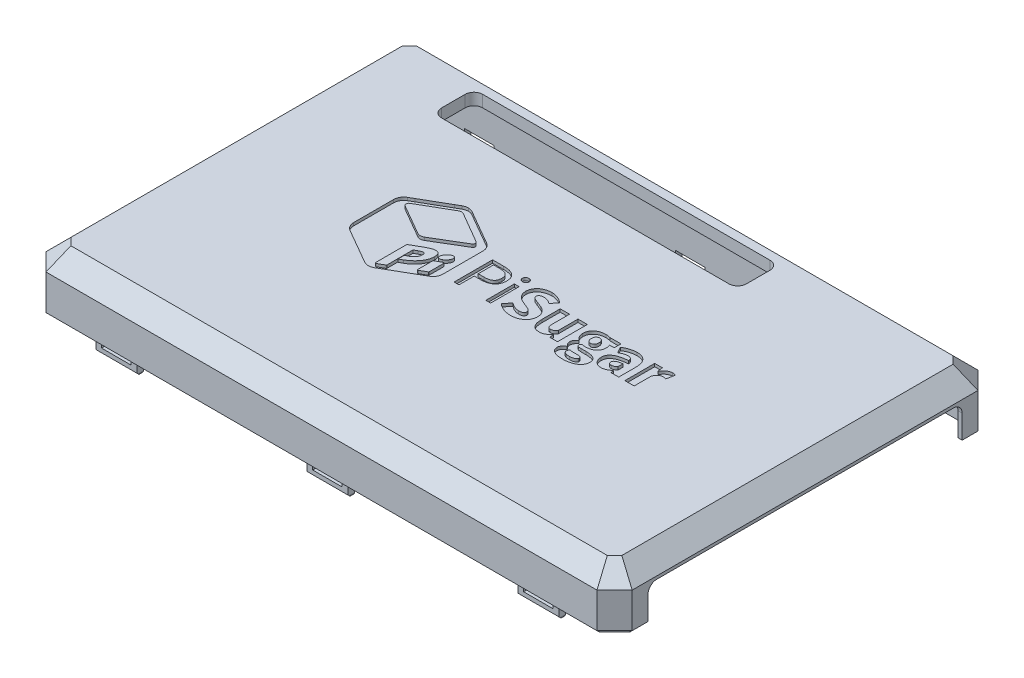
SolidWorks part; units mm, degrees
ref_plane "前视基准面" through (0, 0, 0) normal (0, 0, 1) x (1, 0, 0)
ref_plane "上视基准面" through (0, 0, 0) normal (0, 1, 0) x (1, 0, 0)
ref_plane "右视基准面" through (0, 0, 0) normal (1, 0, 0) x (0, 0, -1)
sketch "草图1" plane through (0, 0, 0) normal (0, 1, 0) x (1, 0, 0)
  line L1 (-50, 32.5) -> (50, 32.5)
  line L2 (-50, 32.5) -> (-50, -32.5)
  line L3 (-50, -32.5) -> (50, -32.5)
  line L4 (50, 32.5) -> (50, -32.5)
  line L5 (-50, 32.5) -> (50, -32.5) construction
  line L6 (-50, -32.5) -> (50, 32.5) construction
  point P0 (0, 0)
  dimension "D1" = 100
  dimension "D2" = 65
extrude "凸台-拉伸1" add sketch "草图1" along normal blind 2
sketch "草图4" plane through (0, 0, 0) normal (0, -1, 0) x (1, 0, 0)
  line L4 (-50, -32.5) -> (50, -32.5)
  line L5 (50, -32.5) -> (50, 32.5)
  line L6 (50, 32.5) -> (-50, 32.5)
  line L7 (-50, 32.5) -> (-50, -32.5)
  line L8 (-47.9, -30.4) -> (47.9, -30.4)
  line L9 (47.9, -30.4) -> (47.9, 30.4)
  line L10 (47.9, 30.4) -> (-47.9, 30.4)
  line L11 (-47.9, 30.4) -> (-47.9, -30.4)
  line L12 (-47.9, -30.4) -> (47.9, -30.4)
  line L13 (47.9, -30.4) -> (47.9, 30.4)
  line L14 (47.9, 30.4) -> (-47.9, 30.4)
  line L15 (-47.9, 30.4) -> (-47.9, -30.4)
  line L16 (-50, -32.5) -> (50, -32.5)
  line L17 (50, -32.5) -> (50, 32.5)
  line L18 (50, 32.5) -> (-50, 32.5)
  line L19 (-50, 32.5) -> (-50, -32.5)
  dimension "D1" = 2.1
  dimension "D2" = 0
extrude "凸台-拉伸2" add sketch "草图4" along normal blind 7
sketch "草图21" plane through (-50, 0, 0) normal (-1, 0, 0) x (0, 0, 1)
  line L0 (-32.5, 2) -> (32.5, 2) construction
  line L1 (-10, -2) -> (10, -2)
  line L2 (-10, -2) -> (-10, -4)
  line L3 (-10, -4) -> (10, -4)
  line L4 (10, -2) -> (10, -4)
  line L5 (-10, -2) -> (10, -4) construction
  line L6 (-10, -4) -> (10, -2) construction
  point P0 (0, -3)
  point P8 (0, 2)
  dimension "D1" = 4
  dimension "D2" = 2
  dimension "D3" = 20
chamfer "倒角4" distance 2 angle 45 4 edges at (47.9, -3.5, -30.4) (-47.9, -3.5, -30.4) (-47.9, -3.5, 30.4) (47.9, -3.5, 30.4)
chamfer "倒角5" distance 3 angle 45 4 edges at (-50, -2.5, -32.5) (-50, -2.5, 32.5) (50, -2.5, -32.5) (50, -2.5, 32.5)
chamfer "倒角7" distance 3 angle 45 8 edges at (48.5, 2, -31) (50, 2, 0) (48.5, 2, 31) (0, 2, 32.5) (-48.5, 2, 31) (-50, 2, 0) (0, 2, -32.5) (-48.5, 2, -31)
sketch "草图24" plane through (47.9, 0, 0) normal (-1, 0, 0) x (0, 0, 1)
  line L0 (-28.4, -7) -> (28.4, -7) construction
  line L1 (-28.3, -7) -> (28.3, -7)
  line L2 (-28.3, -7) -> (-28.3, -1)
  line L3 (-28.3, -1) -> (28.3, -1)
  line L4 (28.3, -7) -> (28.3, -1)
  line L6 (-32.5, -1) -> (-32.5, -7) construction
  line L7 (32.5, -7) -> (32.5, -1) construction
  line L8 (28.2574, 2) -> (-28.2574, 2) construction
  dimension "D1" = 4.2
  dimension "D2" = 4.2
  dimension "D3" = 3
extrude "切除-拉伸8" cut sketch "草图24" against normal blind 1.4
fillet "圆角9" radius 2 2 edges at (48.6, -1, 28.3) (48.6, -1, -28.3)
sketch "草图25" plane through (49.3, 0, 0) normal (-1, 0, 0) x (0, 0, 1)
  line L0 (-32.5, -1) -> (-32.5, -7) construction
  line L1 (32.5, -7) -> (32.5, -1) construction
  line L4 (-28.3, -7) -> (28.3, -7) construction
  line L12 (26.8, -7) -> (26.8, -3)
  line L13 (25.3, -1.5) -> (-25.3, -1.5)
  line L14 (-26.8, -3) -> (-26.8, -7)
  line L15 (-26.8, -7) -> (26.8, -7)
  arc A6 (26.8, -3) -> (25.3, -1.5) centre (25.3, -3) ccw
  arc A7 (-25.3, -1.5) -> (-26.8, -3) centre (-25.3, -3) ccw
  dimension "D1" = 7.2
  dimension "D2" = 7.2
extrude "切除-拉伸9" cut sketch "草图25" against normal blind 11.4
sketch "草图26" plane through (0, -7, 0) normal (0, -1, 0) x (1, 0, 0)
  line L0 (45.9, 30.4) -> (47.9, 28.4)
  line L1 (-45.9, -30.4) -> (45.9, -30.4)
  line L2 (-47.9, -28.4) -> (-47.9, 28.4)
  line L3 (-45.9, 30.4) -> (45.9, 30.4)
  line L5 (-47.9, 28.4) -> (-45.9, 30.4)
  line L6 (-47.9, -28.4) -> (-45.9, -30.4)
  line L7 (45.9, -30.4) -> (47.9, -28.4)
  line L8 (-49, -28.8556) -> (-49, 28.8556)
  line L9 (-49, 28.8556) -> (-46.3556, 31.5)
  line L10 (-46.3556, 31.5) -> (46.3556, 31.5)
  line L11 (46.3556, 31.5) -> (49, 28.8556)
  line L13 (46.3556, -31.5) -> (49, -28.8556)
  line L14 (-46.3556, -31.5) -> (46.3556, -31.5)
  line L15 (-49, -28.8556) -> (-46.3556, -31.5)
  line L16 (45.9, 30.4) -> (-45.9, 30.4) construction
  line L17 (49, -28.8556) -> (49, 28.8556) construction
  line L18 (47.9, -28.4) -> (47.9, 28.4) construction
  line L19 (49, 28.8556) -> (49, 28.3)
  line L21 (49, 28.3) -> (47.9, 28.3)
  line L23 (47.9, 28.3) -> (47.9, 28.4)
  line L24 (49, -28.8556) -> (49, -28.3)
  line L26 (49, -28.3) -> (47.9, -28.3)
  line L28 (47.9, -28.3) -> (47.9, -28.4)
  line L29 (49.3, -28.3) -> (47.9, -28.3) construction
  line L30 (49.3, 28.3) -> (47.9, 28.3) construction
  point P0 (-47.9, -30.4)
  point P1 (47.9, 30.4)
  point P2 (-47.9, 30.4)
  point P3 (47.9, -30.4)
  dimension "D2" = 56.8
  dimension "D7" = 91.8
  dimension "D1" = 1.1
extrude "凸台-拉伸9" add sketch "草图26" along normal blind 1
sketch "草图29" plane through (0, 2, 0) normal (0, 1, 0) x (1, 0, 0)
  line B0 (-10.6869, 6.36) -> (-11.5075, 6.833)
  line B1 (-11.5075, 6.833) -> (-15.7643, 9.2891)
  line B2 (-15.7643, 9.2891) -> (-16.5849, 9.7678)
  line B3 (-18.3059, 9.7678) -> (-19.1266, 9.2891)
  line B4 (-19.1266, 9.2891) -> (-23.3834, 6.833)
  line B5 (-23.3834, 6.833) -> (-24.2041, 6.36)
  line B6 (-25.0646, 4.8726) -> (-25.0646, -1.943)
  line B7 (-24.2041, -3.4303) -> (-23.3834, -3.9033)
  line B8 (-23.3834, -3.9033) -> (-19.1266, -6.3594)
  line B9 (-19.1266, -6.3594) -> (-18.3059, -6.8381)
  line B10 (-16.5849, -6.8381) -> (-15.7643, -6.3594)
  line B11 (-15.7643, -6.3594) -> (-11.5075, -3.9033)
  line B12 (-11.5075, -3.9033) -> (-10.6869, -3.4303)
  line B13 (-9.8264, -1.943) -> (-9.8264, 4.8726)
  line B14 (-23.1099, 5.6818) -> (-17.8444, 8.7249)
  line B15 (-17.0408, 8.7249) -> (-11.8038, 5.6761)
  line B16 (-11.7981, 4.9752) -> (-16.887, 1.9321)
  line B17 (-15.3084, -3.2252) -> (-15.9011, -3.5557)
  line B18 (-15.9582, -3.6526) -> (-15.9582, -5.3622)
  line B19 (-16.0151, -5.459) -> (-17.1206, -6.0859)
  line B20 (-17.2859, -5.989) -> (-17.2859, -0.712)
  line B21 (-17.2289, -0.6152) -> (-15.3484, 0.4505)
  line B22 (-11.4049, -2.8719) -> (-12.499, -3.493)
  line B23 (-12.6643, -3.3961) -> (-12.6643, -0.883)
  line B24 (-12.6073, -0.7861) -> (-11.5132, -0.1707)
  line B25 (-11.3479, -0.2676) -> (-11.3479, -2.775)
  line B26 (-15.3769, -2.2108) -> (-15.9011, -2.4729)
  line B27 (-15.9582, -2.3533) -> (-15.9582, -1.0084)
  line B28 (-15.9011, -0.9115) -> (-15.411, -0.638)
  line B29 (-5.8316, 4.3939) -> (-7.7065, 4.3939)
  line B30 (-7.7065, 4.3939) -> (-7.7065, -2.1709)
  line B31 (-7.7065, -2.1709) -> (-6.8745, -2.1709)
  line B32 (-6.8745, -2.1709) -> (-6.8745, 0.4334)
  line B33 (-6.8745, 0.4334) -> (-5.786, 0.4334)
  line B34 (-5.8942, 1.1058) -> (-6.8745, 1.1058)
  line B35 (-6.8745, 1.1058) -> (-6.8745, 3.7215)
  line B36 (-6.8745, 3.7215) -> (-5.9285, 3.7215)
  line B37 (-2.2928, 2.6957) -> (-2.2928, -2.1709)
  line B38 (-2.2928, -2.1709) -> (-1.4778, -2.1709)
  line B39 (-1.4778, -2.1709) -> (-1.4778, 2.6957)
  line B40 (-1.4778, 2.6957) -> (-2.2928, 2.6957)
  line B41 (3.2292, 1.6187) -> (2.3973, 1.9492)
  line B42 (3.554, 2.7356) -> (4.3519, 3.7386)
  line B43 (1.1208, 0.7753) -> (1.9699, 0.4163)
  line B44 (0.4198, -0.2334) -> (-0.4862, -1.3389)
  line B45 (8.3353, 2.9237) -> (8.3353, -0.4157)
  line B46 (6.8935, -0.0282) -> (6.8935, 2.9237)
  line B47 (6.8935, 2.9237) -> (5.3036, 2.9237)
  line B48 (5.3036, 2.9237) -> (5.3036, -0.2277)
  line B49 (8.4835, -1.47) -> (8.5176, -1.47)
  line B50 (8.5176, -1.47) -> (8.6316, -2.1709)
  line B51 (8.6316, -2.1709) -> (9.9309, -2.1709)
  line B52 (9.9309, -2.1709) -> (9.9309, 2.9237)
  line B53 (9.9309, 2.9237) -> (8.3353, 2.9237)
  line B54 (13.7832, -1.1679) -> (12.9796, -1.1679)
  line B55 (14.8773, 1.7726) -> (15.6637, 1.7726)
  line B56 (15.6637, 1.7726) -> (15.6637, 2.9237)
  line B57 (15.6637, 2.9237) -> (13.7946, 2.9237)
  line B58 (11.5436, -0.1194) -> (11.5436, -0.1536)
  line B59 (11.4467, -1.9829) -> (11.4467, -2.0284)
  line B60 (12.9967, -2.3875) -> (13.4812, -2.3875)
  line B61 (16.1196, 2.3823) -> (16.6781, 1.3338)
  line B62 (18.9234, -1.658) -> (18.9632, -1.658)
  line B63 (18.9632, -1.658) -> (19.0772, -2.1709)
  line B64 (19.0772, -2.1709) -> (20.3765, -2.1709)
  line B65 (20.3765, -2.1709) -> (20.3765, 0.724)
  line B66 (18.7809, 0.1598) -> (18.7809, -0.6551)
  line B67 (22.8669, 2.0404) -> (22.8326, 2.0404)
  line B68 (22.8326, 2.0404) -> (22.7244, 2.9237)
  line B69 (22.7244, 2.9237) -> (21.4251, 2.9237)
  line B70 (21.4251, 2.9237) -> (21.4251, -2.1709)
  line B71 (21.4251, -2.1709) -> (23.0093, -2.1709)
  line B72 (23.0093, -2.1709) -> (23.0093, 0.7411)
  line B73 (24.6676, 1.5731) -> (24.9354, 2.9465)
  line B74 (-15.9011, -2.4729) -> (-15.9011, -3.5557)
  line B75 (-15.9582, -2.3533) -> (-15.9582, -3.6526)
  spline B76 degree 3 poles (-16.5849, 9.7678) (-16.8528, 9.9159) (-17.1491, 9.9957) (-17.4454, 9.9957) knots 3 3 3 3 4 4 4 4
  spline B77 degree 3 poles (-17.4454, 9.9957) (-17.7418, 9.9957) (-18.0381, 9.9159) (-18.3059, 9.7678) knots 4 4 4 4 5 5 5 5
  spline B78 degree 3 poles (-24.2041, 6.36) (-24.734, 6.0523) (-25.0646, 5.4824) (-25.0646, 4.8726) knots 8 8 8 8 9 9 9 9
  spline B79 degree 3 poles (-25.0646, -1.943) (-25.0646, -2.5584) (-24.734, -3.1226) (-24.2041, -3.4303) knots 10 10 10 10 11 11 11 11
  spline B80 degree 3 poles (-18.3059, -6.8381) (-18.0381, -6.992) (-17.7418, -7.0661) (-17.4454, -7.0661) knots 14 14 14 14 15 15 15 15
  spline B81 degree 3 poles (-17.4454, -7.0661) (-17.1491, -7.0661) (-16.8528, -6.992) (-16.5849, -6.8381) knots 15 15 15 15 16 16 16 16
  spline B82 degree 3 poles (-10.6869, -3.4303) (-10.1512, -3.1226) (-9.8264, -2.5584) (-9.8264, -1.943) knots 19 19 19 19 20 20 20 20
  spline B83 degree 3 poles (-9.8264, 4.8726) (-9.8264, 5.4824) (-10.1512, 6.0523) (-10.6869, 6.36) knots 21 21 21 21 22 22 22 22
  spline B84 degree 2 poles (-17.9982, 1.9321) (-23.1498, 4.9068) (-23.1612, 4.9125) knots 0 0 0 1 1 1
  spline B85 degree 3 poles (-23.1612, 4.9125) (-23.429, 5.1063) (-23.4006, 5.5166) (-23.1099, 5.6818) knots 1 1 1 1 2 2 2 2
  spline B86 degree 3 poles (-17.8444, 8.7249) (-17.5993, 8.8674) (-17.2916, 8.8674) (-17.0408, 8.7249) knots 3 3 3 3 4 4 4 4
  spline B87 degree 3 poles (-11.8038, 5.6761) (-11.536, 5.5223) (-11.5303, 5.1348) (-11.7981, 4.9752) knots 5 5 5 5 6 6 6 6
  spline B88 degree 3 poles (-16.887, 1.9321) (-17.2289, 1.7327) (-17.6563, 1.7327) (-17.9982, 1.9321) knots 7 7 7 7 8 8 8 8
  spline B89 degree 3 poles (-15.9582, -5.3622) (-15.9582, -5.4021) (-15.9752, -5.4363) (-16.0151, -5.459) knots 3 3 3 3 4 4 4 4
  spline B90 degree 3 poles (-17.1206, -6.0859) (-17.1947, -6.1258) (-17.2859, -6.0745) (-17.2859, -5.989) knots 5 5 5 5 6 6 6 6
  spline B91 degree 3 poles (-17.2859, -0.712) (-17.2859, -0.6721) (-17.2688, -0.6323) (-17.2289, -0.6152) knots 7 7 7 7 8 8 8 8
  spline B92 degree 3 poles (-15.3484, 0.4505) (-14.1288, 1.14) (-13.1202, 1.2768) (-13.1202, -0.0909) knots 9 9 9 9 10 10 10 10
  spline B93 degree 3 poles (-13.1202, -0.0909) (-13.1202, -1.4073) (-14.1402, -2.5641) (-15.3084, -3.2252) knots 10 10 10 10 11 11 11 11
  spline B94 degree 3 poles (-11.3479, -2.775) (-11.3479, -2.8148) (-11.3707, -2.8547) (-11.4049, -2.8719) knots 0 0 0 0 1 1 1 1
  spline B95 degree 3 poles (-12.499, -3.493) (-12.5731, -3.5329) (-12.6643, -3.4816) (-12.6643, -3.3961) knots 2 2 2 2 3 3 3 3
  spline B96 degree 3 poles (-12.6643, -0.883) (-12.6643, -0.8431) (-12.6415, -0.8089) (-12.6073, -0.7861) knots 4 4 4 4 5 5 5 5
  spline B97 degree 3 poles (-11.5132, -0.1707) (-11.4391, -0.1308) (-11.3479, -0.1821) (-11.3479, -0.2676) knots 6 6 6 6 7 7 7 7
  spline B98 degree 3 poles (-12.0033, 1.499) (-11.5644, 1.7498) (-11.2511, 1.6415) (-11.2511, 1.2426) (-11.2511, 0.8494) (-11.5644, 0.3878) (-12.0033, 0.1428) knots 2 2 2 2 3 3 3 4 4 4 4
  spline B99 degree 3 poles (-12.0033, 0.1428) (-12.4477, -0.1137) (-12.7611, -0.0054) (-12.7611, 0.3878) (-12.7611, 0.7924) (-12.4477, 1.2483) (-12.0033, 1.499) knots 0 0 0 0 1 1 1 2 2 2 2
  spline B100 degree 3 poles (-14.4195, -0.826) (-14.4195, -1.3674) (-14.7272, -1.8461) (-15.3769, -2.2108) knots 0 0 0 0 1 1 1 1
  spline B101 degree 3 poles (-15.9582, -1.0084) (-15.9582, -0.9685) (-15.9353, -0.9286) (-15.9011, -0.9115) knots 4 4 4 4 5 5 5 5
  spline B102 degree 3 poles (-15.411, -0.638) (-14.7728, -0.2733) (-14.4195, -0.2676) (-14.4195, -0.826) knots 6 6 6 6 7 7 7 7
  spline B103 degree 3 poles (-5.786, 0.4334) (-4.3556, 0.4334) (-3.3698, 1.083) (-3.3698, 2.4678) knots 5 5 5 5 6 6 6 6
  spline B104 degree 3 poles (-3.3698, 2.4678) (-3.3698, 3.9039) (-4.3556, 4.3939) (-5.8316, 4.3939) knots 6 6 6 6 7 7 7 7
  spline B105 degree 3 poles (-5.9285, 3.7215) (-4.7773, 3.7215) (-4.1961, 3.4195) (-4.1961, 2.4678) knots 3 3 3 3 4 4 4 4
  spline B106 degree 3 poles (-4.1961, 2.4678) (-4.1961, 1.5275) (-4.7375, 1.1058) (-5.8942, 1.1058) knots 4 4 4 4 5 5 5 5
  spline B107 degree 3 poles (-1.8824, 3.6987) (-1.5576, 3.6987) (-1.3183, 3.921) (-1.3183, 4.223) (-1.3183, 4.5592) (-1.5576, 4.7529) (-1.8824, 4.7529) knots 2 2 2 2 3 3 3 4 4 4 4
  spline B108 degree 3 poles (-1.8824, 4.7529) (-2.2072, 4.7529) (-2.4466, 4.5592) (-2.4466, 4.223) (-2.4466, 3.921) (-2.2072, 3.6987) (-1.8824, 3.6987) knots 0 0 0 0 1 1 1 2 2 2 2
  spline B109 degree 3 poles (2.3973, 1.9492) (1.8103, 2.1829) (1.3886, 2.3253) (1.3886, 2.6957) knots 1 1 1 1 2 2 2 2
  spline B110 degree 3 poles (1.3886, 2.6957) (1.3886, 3.0491) (1.6906, 3.2485) (2.1864, 3.2485) knots 2 2 2 2 3 3 3 3
  spline B111 degree 3 poles (2.1864, 3.2485) (2.7049, 3.2485) (3.1153, 3.0719) (3.554, 2.7356) knots 3 3 3 3 4 4 4 4
  spline B112 degree 3 poles (4.3519, 3.7386) (3.7707, 4.3255) (2.9557, 4.6219) (2.1864, 4.6219) knots 5 5 5 5 6 6 6 6
  spline B113 degree 3 poles (2.1864, 4.6219) (0.7675, 4.6219) (-0.2355, 3.7215) (-0.2355, 2.6046) knots 6 6 6 6 7 7 7 7
  spline B114 degree 3 poles (-0.2355, 2.6046) (-0.2355, 1.6358) (0.4198, 1.0545) (1.1208, 0.7753) knots 7 7 7 7 8 8 8 8
  spline B115 degree 3 poles (1.9699, 0.4163) (2.5397, 0.1769) (2.9102, 0.0516) (2.9102, -0.3359) knots 9 9 9 9 10 10 10 10
  spline B116 degree 3 poles (2.9102, -0.3359) (2.9102, -0.695) (2.6309, -0.9172) (2.0382, -0.9172) knots 10 10 10 10 11 11 11 11
  spline B117 degree 3 poles (2.0382, -0.9172) (1.514, -0.9172) (0.8928, -0.638) (0.4198, -0.2334) knots 11 11 11 11 12 12 12 12
  spline B118 degree 3 poles (-0.4862, -1.3389) (0.2033, -1.9715) (1.1378, -2.2963) (2.004, -2.2963) knots 13 13 13 13 14 14 14 14
  spline B119 degree 3 poles (2.004, -2.2963) (3.6168, -2.2963) (4.5513, -1.3218) (4.5513, -0.2106) knots 14 14 14 14 15 15 15 15
  spline B120 degree 3 poles (4.5513, -0.2106) (4.5513, 0.7297) (4.0556, 1.2882) (3.2292, 1.6187) knots 15 15 15 15 16 16 16 16
  spline B121 degree 3 poles (8.3353, -0.4157) (8.0675, -0.7918) (7.8451, -0.9343) (7.4862, -0.9343) knots 1 1 1 1 2 2 2 2
  spline B122 degree 3 poles (7.4862, -0.9343) (7.0815, -0.9343) (6.8935, -0.7349) (6.8935, -0.0282) knots 2 2 2 2 3 3 3 3
  spline B123 degree 3 poles (5.3036, -0.2277) (5.3036, -1.4985) (5.7766, -2.2963) (6.8878, -2.2963) knots 6 6 6 6 7 7 7 7
  spline B124 degree 3 poles (6.8878, -2.2963) (7.583, -2.2963) (8.0618, -1.9715) (8.4835, -1.47) knots 7 7 7 7 8 8 8 8
  spline B125 degree 3 poles (12.9796, -1.1679) (12.4326, -1.1679) (12.2274, -1.0597) (12.2274, -0.826) knots 1 1 1 1 2 2 2 2
  spline B126 degree 3 poles (12.2274, -0.826) (12.2274, -0.6551) (12.2673, -0.5753) (12.387, -0.467) knots 2 2 2 2 3 3 3 3
  spline B127 degree 3 poles (12.387, -0.467) (12.6093, -0.5297) (12.8144, -0.5582) (12.9853, -0.5582) knots 3 3 3 3 4 4 4 4
  spline B128 degree 3 poles (12.9853, -0.5582) (14.1137, -0.5582) (15.0198, -0.0396) (15.0198, 1.1514) knots 4 4 4 4 5 5 5 5
  spline B129 degree 3 poles (15.0198, 1.1514) (15.0198, 1.3965) (14.9571, 1.6301) (14.8773, 1.7726) knots 5 5 5 5 6 6 6 6
  spline B130 degree 3 poles (13.7946, 2.9237) (13.5609, 3.0092) (13.2817, 3.0491) (12.9853, 3.0491) knots 9 9 9 9 10 10 10 10
  spline B131 degree 3 poles (12.9853, 3.0491) (11.8855, 3.0491) (10.854, 2.445) (10.854, 1.197) knots 10 10 10 10 11 11 11 11
  spline B132 degree 3 poles (10.854, 1.197) (10.854, 0.6043) (11.1846, 0.1313) (11.5436, -0.1194) knots 11 11 11 11 12 12 12 12
  spline B133 degree 3 poles (11.5436, -0.1536) (11.2131, -0.3872) (10.9794, -0.7462) (10.9794, -1.1053) knots 13 13 13 13 14 14 14 14
  spline B134 degree 3 poles (10.9794, -1.1053) (10.9794, -1.5327) (11.1789, -1.8005) (11.4467, -1.9829) knots 14 14 14 14 15 15 15 15
  spline B135 degree 3 poles (11.4467, -2.0284) (10.9737, -2.2678) (10.723, -2.6097) (10.723, -3.0314) knots 16 16 16 16 17 17 17 17
  spline B136 degree 3 poles (10.723, -3.0314) (10.723, -3.9432) (11.686, -4.3136) (12.86, -4.3136) knots 17 17 17 17 18 18 18 18
  spline B137 degree 3 poles (12.86, -4.3136) (14.6323, -4.3136) (15.7435, -3.55) (15.7435, -2.4729) knots 18 18 18 18 19 19 19 19
  spline B138 degree 3 poles (15.7435, -2.4729) (15.7435, -1.5498) (15.0369, -1.1679) (13.7832, -1.1679) knots 19 19 19 19 20 20 20 20
  spline B139 degree 3 poles (12.9853, 0.3992) (12.6207, 0.3992) (12.3415, 0.667) (12.3415, 1.197) (12.3415, 1.7156) (12.6207, 1.9834) (12.9853, 1.9834) knots 2 2 2 2 3 3 3 4 4 4 4
  spline B140 degree 3 poles (12.9853, 1.9834) (13.3615, 1.9834) (13.6293, 1.7156) (13.6293, 1.197) (13.6293, 0.667) (13.3615, 0.3992) (12.9853, 0.3992) knots 0 0 0 0 1 1 1 2 2 2 2
  spline B141 degree 3 poles (13.1107, -3.3163) (12.4554, -3.3163) (12.028, -3.1397) (12.028, -2.7807) knots 0 0 0 0 1 1 1 1
  spline B142 degree 3 poles (12.028, -2.7807) (12.028, -2.6097) (12.1077, -2.4672) (12.2673, -2.3248) knots 1 1 1 1 2 2 2 2
  spline B143 degree 3 poles (12.2673, -2.3248) (12.4326, -2.3704) (12.6264, -2.3875) (12.9967, -2.3875) knots 2 2 2 2 3 3 3 3
  spline B144 degree 3 poles (13.4812, -2.3875) (13.9541, -2.3875) (14.222, -2.4501) (14.222, -2.7522) knots 4 4 4 4 5 5 5 5
  spline B145 degree 3 poles (14.222, -2.7522) (14.222, -3.077) (13.7661, -3.3163) (13.1107, -3.3163) knots 5 5 5 5 6 6 6 6
  spline B146 degree 3 poles (18.3136, 3.0491) (17.5214, 3.0491) (16.7921, 2.7812) (16.1196, 2.3823) knots 0 0 0 0 1 1 1 1
  spline B147 degree 3 poles (16.6781, 1.3338) (17.1853, 1.6187) (17.607, 1.7783) (18.0116, 1.7783) knots 2 2 2 2 3 3 3 3
  spline B148 degree 3 poles (18.0116, 1.7783) (18.5301, 1.7783) (18.7467, 1.5389) (18.7809, 1.1286) knots 3 3 3 3 4 4 4 4
  spline B149 degree 3 poles (18.7809, 1.1286) (16.7921, 0.9121) (15.9486, 0.3308) (15.9486, -0.7462) knots 4 4 4 4 5 5 5 5
  spline B150 degree 3 poles (15.9486, -0.7462) (15.9486, -1.5953) (16.5242, -2.2963) (17.4645, -2.2963) knots 5 5 5 5 6 6 6 6
  spline B151 degree 3 poles (17.4645, -2.2963) (18.0287, -2.2963) (18.5017, -2.0341) (18.9234, -1.658) knots 6 6 6 6 7 7 7 7
  spline B152 degree 3 poles (20.3765, 0.724) (20.3765, 2.3196) (19.63, 3.0491) (18.3136, 3.0491) knots 11 11 11 11 12 12 12 12
  spline B153 degree 3 poles (18.7809, -0.6551) (18.5472, -0.9058) (18.3364, -1.0597) (18.0116, -1.0597) knots 0 0 0 0 1 1 1 1
  spline B154 degree 3 poles (18.0116, -1.0597) (17.681, -1.0597) (17.4645, -0.9172) (17.4645, -0.6209) knots 1 1 1 1 2 2 2 2
  spline B155 degree 3 poles (17.4645, -0.6209) (17.4645, -0.2619) (17.7893, 0.0231) (18.7809, 0.1598) knots 2 2 2 2 3 3 3 3
  spline B156 degree 3 poles (24.32, 3.0491) (23.8071, 3.0491) (23.2429, 2.7185) (22.8669, 2.0404) knots 0 0 0 0 1 1 1 1
  spline B157 degree 3 poles (23.0093, 0.7411) (23.2771, 1.4135) (23.7331, 1.6529) (24.1091, 1.6529) knots 7 7 7 7 8 8 8 8
  spline B158 degree 3 poles (24.1091, 1.6529) (24.3371, 1.6529) (24.4853, 1.6187) (24.6676, 1.5731) knots 8 8 8 8 9 9 9 9
  spline B159 degree 3 poles (24.9354, 2.9465) (24.7929, 3.0092) (24.622, 3.0491) (24.32, 3.0491) knots 10 10 10 10 11 11 11 11
sketch_block_instance "块1-2"
sketch_block "块1"
extrude "切除-拉伸12" cut sketch "草图29" against normal blind 0.5
sketch "草图30" plane through (0, 0, 0) normal (0, -1, 0) x (1, 0, 0)
  line L0 (50, 25.3) -> (50, -25.3) construction
  line L1 (45.3834, 10.75) -> (47.8, 10.75)
  line L2 (45.3834, 10.75) -> (45.3834, 9.25)
  line L3 (45.3834, 9.25) -> (47.8, 9.25)
  line L4 (47.8, 10.75) -> (47.8, 9.25)
  line L5 (45.3834, -7.25) -> (47.8, -7.25)
  line L6 (45.3834, -7.25) -> (45.3834, -8.75)
  line L7 (45.3834, -8.75) -> (47.8, -8.75)
  line L8 (47.8, -7.25) -> (47.8, -8.75)
  dimension "D1" = 2.2
  dimension "D2" = 2.4166
  dimension "D3" = 1.5
  dimension "D4" = 1.5
extrude "凸台-拉伸10" add sketch "草图30" along normal blind 3.3
chamfer "倒角8" distance 1 angle 45 2 edges at (47.8, -3.3, 10) (47.8, -3.3, -8)
sketch "草图31" plane through (0, 2, 0) normal (0, 1, 0) x (1, 0, 0)
  line L0 (-47, 32.5) -> (47, 32.5) construction
  line L1 (-34.5, 28) -> (17.5, 28)
  line L2 (-34.5, 28) -> (-34.5, 21)
  line L3 (-34.5, 21) -> (17.5, 21)
  line L4 (17.5, 28) -> (17.5, 21)
  line L5 (50, 29.5) -> (50, -29.5) construction
  dimension "D1" = 4.5
  dimension "D2" = 32.5
  dimension "D3" = 52
  dimension "D4" = 7
extrude "切除-拉伸13" cut sketch "草图31" against normal up to next
fillet "圆角10" radius 1.5 4 edges at (17.5, 1, -21) (-34.5, 1, -21) (-34.5, 1, -28) (17.5, 1, -28)
sketch "草图33" plane through (-47.9, 0, 0) normal (1, 0, 0) x (0, 0, -1)
  line L1 (-7.5, -10) -> (-6, -10)
  line L2 (-7.5, -10) -> (-7.5, 0)
  line L3 (-7.5, 0) -> (-6, 0)
  line L4 (-6, -10) -> (-6, 0)
  line L6 (6, -10) -> (7.5, -10)
  line L7 (6, -10) -> (6, 0)
  line L8 (6, 0) -> (7.5, 0)
  line L9 (7.5, -10) -> (7.5, 0)
  line L10 (-32.5, -7) -> (-32.5, -1) construction
  line L11 (32.5, -1) -> (32.5, -7) construction
  line L12 (26.5, 0) -> (28, 0) construction
  line L13 (-28.4, 0) -> (28.4, 0) construction
  dimension "D1" = 25
  dimension "D2" = 25
  dimension "D3" = 10
  dimension "D4" = 1.5
extrude "凸台-拉伸11" add sketch "草图33" along normal blind 2
extrude "切除-拉伸15" cut sketch "草图21" against normal blind 5
fillet "圆角11" radius 1 4 edges at (-48.95, -2, -10) (-48.95, -4, -10) (-48.95, -2, 10) (-48.95, -4, 10)
chamfer "倒角9" distance 1 angle 45 2 edges at (-47.9, -10, 6.75) (-47.9, -10, -6.75)
chamfer "倒角10" distance 0.8 angle 45 10 edges at (46.9, 0, -29.4) (47.9, 0, 0) (46.9, 0, 29.4) (0, 0, 30.4) (-46.9, 0, 29.4) (-47.9, 0, 17.95) (-47.9, 0, 0) (-47.9, 0, -17.95) (0, 0, -30.4) (-46.9, 0, -29.4)
sketch "草图34" plane through (0, 0, -30.4) normal (0, 0, 1) x (1, 0, 0)
  line L0 (47, -7) -> (-47, -7) construction
  line L1 (32.5, -7) -> (39.5, -7)
  line L2 (32.5, -7) -> (32.5, -9.8)
  line L3 (32.5, -9.8) -> (39.5, -9.8)
  line L4 (39.5, -7) -> (39.5, -9.8)
  line L5 (50, -1) -> (50, -7) construction
  line L6 (-3.5, -7) -> (3.5, -7)
  line L7 (-3.5, -7) -> (-3.5, -9.8)
  line L8 (-3.5, -9.8) -> (3.5, -9.8)
  line L9 (3.5, -7) -> (3.5, -9.8)
  line L10 (-39.5, -7) -> (-32.5, -7)
  line L11 (-39.5, -7) -> (-39.5, -9.8)
  line L12 (-39.5, -9.8) -> (-32.5, -9.8)
  line L13 (-32.5, -7) -> (-32.5, -9.8)
  dimension "D1" = 10.5
  dimension "D2" = 7
  dimension "D3" = 29
  dimension "D4" = 2.8
  dimension "D5" = 29
extrude "凸台-拉伸12" add sketch "草图34" against normal blind 1.1
sketch "草图35" plane through (0, 0, 30.4) normal (0, 0, -1) x (-1, 0, 0)
  line L4 (39.5, -7) -> (32.5, -7)
  line L5 (32.5, -7) -> (32.5, -9.8)
  line L6 (32.5, -9.8) -> (39.5, -9.8)
  line L7 (39.5, -9.8) -> (39.5, -7)
  line L8 (39.5, -7) -> (32.5, -7)
  line L9 (32.5, -7) -> (32.5, -9.8)
  line L10 (32.5, -9.8) -> (39.5, -9.8)
  line L11 (39.5, -9.8) -> (39.5, -7)
  line L12 (3.5, -7) -> (-3.5, -7)
  line L13 (-3.5, -7) -> (-3.5, -9.8)
  line L14 (-3.5, -9.8) -> (3.5, -9.8)
  line L15 (3.5, -9.8) -> (3.5, -7)
  line L16 (3.5, -7) -> (-3.5, -7)
  line L17 (-3.5, -7) -> (-3.5, -9.8)
  line L18 (-3.5, -9.8) -> (3.5, -9.8)
  line L19 (3.5, -9.8) -> (3.5, -7)
  line L20 (-32.5, -7) -> (-39.5, -7)
  line L21 (-39.5, -7) -> (-39.5, -9.8)
  line L22 (-39.5, -9.8) -> (-32.5, -9.8)
  line L23 (-32.5, -9.8) -> (-32.5, -7)
  line L24 (-32.5, -7) -> (-39.5, -7)
  line L25 (-39.5, -7) -> (-39.5, -9.8)
  line L26 (-39.5, -9.8) -> (-32.5, -9.8)
  line L27 (-32.5, -9.8) -> (-32.5, -7)
  dimension "D1" = 0
  dimension "D2" = 0
  dimension "D3" = 0
extrude "凸台-拉伸13" add sketch "草图35" against normal blind 1.1
sketch "草图36" plane through (0, 0, 31.5) normal (0, 0, 1) x (1, 0, 0)
  line L0 (46.3556, -7) -> (-46.3556, -7) construction
  line L1 (-33.5, -7) -> (-38.5, -7)
  line L2 (-33.5, -7) -> (-33.5, -8.5)
  line L3 (-33.5, -8.5) -> (-38.5, -8.5)
  line L4 (-38.5, -7) -> (-38.5, -8.5)
  line L5 (-50, -7) -> (-50, -1) construction
  line L6 (2.5, -7) -> (-2.5, -7)
  line L7 (2.5, -7) -> (2.5, -8.5)
  line L8 (2.5, -8.5) -> (-2.5, -8.5)
  line L9 (-2.5, -7) -> (-2.5, -8.5)
  line L10 (38.5, -7) -> (33.5, -7)
  line L11 (38.5, -7) -> (38.5, -8.5)
  line L12 (38.5, -8.5) -> (33.5, -8.5)
  line L13 (33.5, -7) -> (33.5, -8.5)
  dimension "D1" = 11.5
  dimension "D2" = 5
  dimension "D3" = 1.5
  dimension "D4" = 31
  dimension "D5" = 31
extrude "切除-拉伸16" cut sketch "草图36" against normal up to next
sketch "草图37" plane through (0, 0, -31.5) normal (0, 0, -1) x (-1, 0, 0)
  line L4 (-33.5, -7) -> (-38.5, -7)
  line L5 (-33.5, -8.5) -> (-33.5, -7)
  line L6 (-38.5, -8.5) -> (-33.5, -8.5)
  line L7 (-38.5, -7) -> (-38.5, -8.5)
  line L8 (-33.5, -7) -> (-38.5, -7)
  line L9 (-33.5, -8.5) -> (-33.5, -7)
  line L10 (-38.5, -8.5) -> (-33.5, -8.5)
  line L11 (-38.5, -7) -> (-38.5, -8.5)
  line L12 (2.5, -7) -> (-2.5, -7)
  line L13 (2.5, -8.5) -> (2.5, -7)
  line L14 (-2.5, -8.5) -> (2.5, -8.5)
  line L15 (-2.5, -7) -> (-2.5, -8.5)
  line L16 (2.5, -7) -> (-2.5, -7)
  line L17 (2.5, -8.5) -> (2.5, -7)
  line L18 (-2.5, -8.5) -> (2.5, -8.5)
  line L19 (-2.5, -7) -> (-2.5, -8.5)
  line L20 (38.5, -7) -> (33.5, -7)
  line L21 (38.5, -8.5) -> (38.5, -7)
  line L22 (33.5, -8.5) -> (38.5, -8.5)
  line L23 (33.5, -7) -> (33.5, -8.5)
  line L24 (38.5, -7) -> (33.5, -7)
  line L25 (38.5, -8.5) -> (38.5, -7)
  line L26 (33.5, -8.5) -> (38.5, -8.5)
  line L27 (33.5, -7) -> (33.5, -8.5)
  dimension "D1" = 0
  dimension "D2" = 0
  dimension "D3" = 0
extrude "切除-拉伸17" cut sketch "草图37" against normal up to next
chamfer "倒角11" distance 0.6 angle 45 6 edges at (36, -9.8, -31.5) (0, -9.8, -31.5) (-36, -9.8, -31.5) (36, -9.8, 31.5) (0, -9.8, 31.5) (-36, -9.8, 31.5)
fillet "圆角12" radius 0.4 12 edges at (39.5, -9.8, 30.65) (32.5, -9.8, 30.65) (-3.5, -9.8, 30.65) (3.5, -9.8, 30.65) (-32.5, -9.8, 30.65) (-39.5, -9.8, 30.65) (-39.5, -9.8, -30.65) (-32.5, -9.8, -30.65) (3.5, -9.8, -30.65) (-3.5, -9.8, -30.65) (32.5, -9.8, -30.65) (39.5, -9.8, -30.65)
